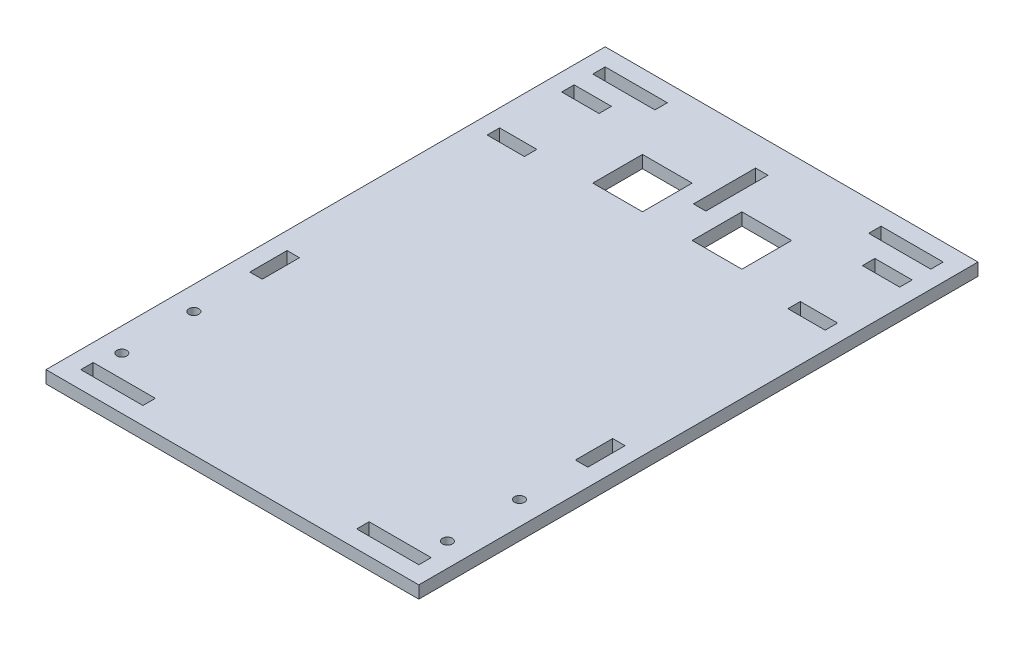
SolidWorks part; units mm, degrees
ref_plane "Front Plane" through (0, 0, 0) normal (0, 0, 1) x (1, 0, 0)
ref_plane "Top Plane" through (0, 0, 0) normal (0, 1, 0) x (1, 0, 0)
ref_plane "Right Plane" through (0, 0, 0) normal (1, 0, 0) x (0, 0, -1)
sketch "Sketch1" plane through (0, 0, 0) normal (0, 1, 0) x (1, 0, 0)
  line L1 (-75, 112.5) -> (75, 112.5)
  line L2 (-75, 112.5) -> (-75, -112.5)
  line L3 (-75, -112.5) -> (75, -112.5)
  line L4 (75, 112.5) -> (75, -112.5)
  point P4 (0, 112.5)
  point P6 (-75, 0)
  dimension "D1" = 150
  dimension "D2" = 225
extrude "Boss-Extrude1" add sketch "Sketch1" along normal blind 5
sketch "Sketch10" plane through (0, 5, 0) normal (0, 1, 0) x (1, 0, 0)
  line L0 (0, 0) -> (-75, 0) construction
  line L1 (-68, -105.5) -> (-43, -105.5)
  line L2 (-68, -105.5) -> (-68, -100.5)
  line L3 (-68, -100.5) -> (-43, -100.5)
  line L4 (-43, -105.5) -> (-43, -100.5)
  line L9 (-75, 112.5) -> (-75, -112.5) construction
  line L10 (0, 0) -> (0, -112.5) construction
  line L11 (-75, -112.5) -> (75, -112.5) construction
  line L12 (-68, 100.5) -> (-43, 100.5)
  line L13 (-43, 105.5) -> (-43, 100.5)
  line L14 (-68, 105.5) -> (-43, 105.5)
  line L15 (-68, 105.5) -> (-68, 100.5)
  line L16 (68, -100.5) -> (43, -100.5)
  line L17 (43, -105.5) -> (43, -100.5)
  line L18 (68, -105.5) -> (43, -105.5)
  line L19 (68, -105.5) -> (68, -100.5)
  line L20 (68, 105.5) -> (68, 100.5)
  line L21 (68, 105.5) -> (43, 105.5)
  line L22 (43, 105.5) -> (43, 100.5)
  line L23 (68, 100.5) -> (43, 100.5)
  dimension "D1" = 7
  dimension "D2" = 7
  dimension "D3" = 5
  dimension "D4" = 25
extrude "Cut-Extrude5" cut sketch "Sketch10" against normal up to surface (5 mm away) up to face at (0, 0, 0)
sketch "Sketch11" plane through (0, 5, 0) normal (0, 1, 0) x (1, 0, 0)
  line L0 (-68, 105.5) -> (-68, 100.5) construction
  line L1 (-68, 93) -> (-53, 93)
  line L2 (-68, 93) -> (-68, 88)
  line L3 (-68, 88) -> (-53, 88)
  line L4 (-53, 93) -> (-53, 88)
  line L5 (0, 0) -> (0, 112.5) construction
  line L6 (75, 112.5) -> (-75, 112.5) construction
  line L7 (68, 88) -> (53, 88)
  line L8 (53, 93) -> (53, 88)
  line L9 (68, 93) -> (53, 93)
  line L10 (68, 93) -> (68, 88)
  line L11 (-68, 58) -> (-53, 58)
  line L12 (-68, 58) -> (-68, 63)
  line L13 (-68, 63) -> (-53, 63)
  line L14 (-53, 58) -> (-53, 63)
  line L15 (68, 58) -> (68, 63)
  line L16 (68, 63) -> (53, 63)
  line L17 (53, 58) -> (53, 63)
  line L18 (68, 58) -> (53, 58)
  dimension "D1" = 7.5
  dimension "D2" = 5
  dimension "D3" = 15
  dimension "D4" = 25
  dimension "D5" = 15
  dimension "D6" = 5
extrude "Cut-Extrude6" cut sketch "Sketch11" against normal up to surface (5 mm away) up to face at (-55.5, 0, -103)
sketch "Sketch12" plane through (0, 5, 0) normal (0, 1, 0) x (1, 0, 0)
  line L0 (0, 0) -> (0, -112.5) construction
  line L1 (-75, -112.5) -> (75, -112.5) construction
  line L3 (-68, -22.5) -> (-63, -22.5)
  line L4 (-68, -22.5) -> (-68, -37.5)
  line L5 (-68, -37.5) -> (-63, -37.5)
  line L6 (-63, -22.5) -> (-63, -37.5)
  line L7 (68, -37.5) -> (63, -37.5)
  line L8 (63, -22.5) -> (63, -37.5)
  line L9 (68, -22.5) -> (63, -22.5)
  line L10 (68, -22.5) -> (68, -37.5)
  line L11 (-68, -100.5) -> (-68, -105.5) construction
  dimension "D1" = 5
  dimension "D2" = 15
  dimension "D4" = 63
extrude "Cut-Extrude7" cut sketch "Sketch12" against normal up to surface (5 mm away) up to face at (60.5, 0, -90.5)
sketch "Sketch13" plane through (0, 5, 0) normal (0, 1, 0) x (1, 0, 0)
  line L0 (0, 0) -> (0, -112.5) construction
  line L1 (-75, -112.5) -> (75, -112.5) construction
  line L13 (-68, -37.5) -> (-63, -37.5) construction
  circle A0 centre (-65.5, -62.5) radius 2
  circle A1 centre (-65.5, -91.5) radius 2
  circle A2 centre (65.5, -91.5) radius 2
  circle A3 centre (65.5, -62.5) radius 2
  point P15 (-65.5, -37.5)
  dimension "D1" = 4
  dimension "D2" = 29
  dimension "D3" = 25
extrude "Cut-Extrude8" cut sketch "Sketch13" against normal up to surface (5 mm away) up to face at (-65.5, 0, 30)
sketch "Sketch14" plane through (0, 5, 0) normal (0, 1, 0) x (1, 0, 0)
  line L0 (0, 112.5) -> (0, 0) construction
  line L1 (75, 112.5) -> (-75, 112.5) construction
  line L2 (30, 62.5) -> (10, 62.5)
  line L3 (-30, 82.5) -> (-10, 82.5)
  line L4 (-30, 82.5) -> (-30, 62.5)
  line L5 (-30, 62.5) -> (-10, 62.5)
  line L6 (-10, 82.5) -> (-10, 62.5)
  line L7 (10, 82.5) -> (10, 62.5)
  line L8 (30, 82.5) -> (10, 82.5)
  line L9 (30, 82.5) -> (30, 62.5)
  dimension "D1" = 20
  dimension "D2" = 45
  dimension "D3" = 20
  dimension "D4" = 30
extrude "Cut-Extrude9" cut sketch "Sketch14" against normal up to surface (5 mm away) up to face at (65.5, 0, 64.5)
sketch "Sketch15" plane through (0, 5, 0) normal (0, 1, 0) x (1, 0, 0)
  line L0 (-43, 100.5) -> (43, 100.5) construction
  line L1 (-2.5, 100.5) -> (2.5, 100.5)
  line L2 (2.5, 100.5) -> (2.5, 75.5)
  line L3 (2.5, 75.5) -> (-2.5, 75.5)
  line L4 (-2.5, 75.5) -> (-2.5, 100.5)
  point P6 (0, 100.5)
  point P9 (0, 100.5)
  dimension "D1" = 5
  dimension "D2" = 25
extrude "Cut-Extrude10" cut sketch "Sketch15" against normal up to surface (5 mm away) up to face at (-20, 0, -72.5)
